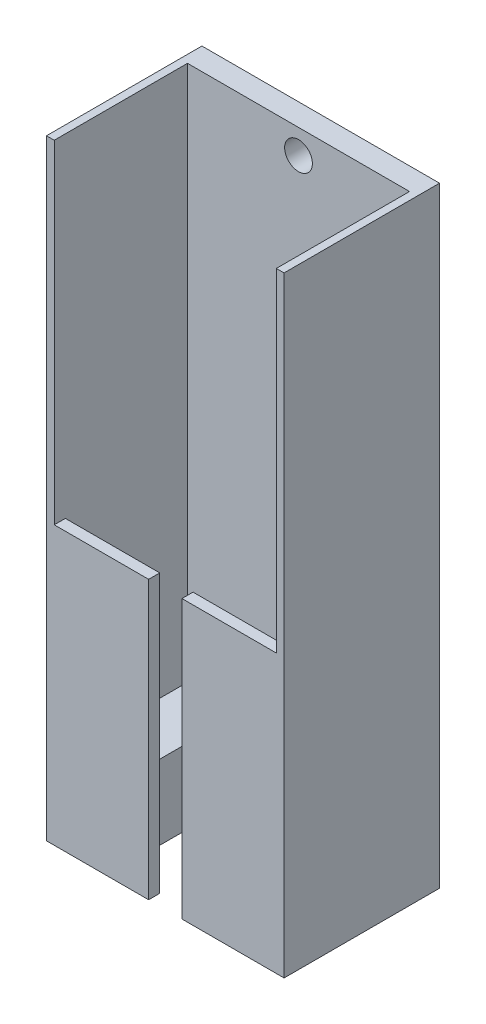
SolidWorks part; units mm, degrees
ref_plane "Front Plane" through (0, 0, 0) normal (0, 0, 1) x (1, 0, 0)
ref_plane "Top Plane" through (0, 0, 0) normal (0, 1, 0) x (1, 0, 0)
ref_plane "Right Plane" through (0, 0, 0) normal (1, 0, 0) x (0, 0, -1)
sketch "Sketch1" plane through (0, 0, 0) normal (0, 0, 1) x (1, 0, 0)
  line L1 (0, 0) -> (54.356, 0)
  line L2 (0, 0) -> (0, -139.7)
  line L3 (0, -139.7) -> (54.356, -139.7)
  line L4 (54.356, 0) -> (54.356, -139.7)
  dimension "D1" = 54.356
  dimension "D2" = 139.7
extrude "Boss-Extrude1" add sketch "Sketch1" along normal blind 35.56
ref_plane "Plane1" through (0, 0, 5.08) normal (0, 0, -1) x (-1, 0, 0)
sketch "Sketch2" plane through (0, 0, 5.08) normal (0, 0, -1) x (-1, 0, 0)
  line L1 (-1.778, -33.02) -> (-52.578, -33.02)
  line L2 (-1.778, -33.02) -> (-1.778, -122.6312)
  line L3 (-1.778, -122.6312) -> (-13.843, -122.6312)
  line L4 (-52.578, -33.02) -> (-52.578, -122.6312)
  line L5 (-1.778, -33.02) -> (-52.578, -122.6312) construction
  line L6 (-1.778, -122.6312) -> (-52.578, -33.02) construction
  line L8 (-54.356, 0) -> (0, 0) construction
  line L10 (0, -139.7) -> (-54.356, -139.7) construction
  line L11 (-13.843, -139.7) -> (-40.513, -139.7)
  line L12 (-13.843, -139.7) -> (-13.843, -122.6312)
  line L14 (-40.513, -139.7) -> (-40.513, -122.6312)
  line L15 (-13.843, -139.7) -> (-40.513, -122.6312) construction
  line L16 (-13.843, -122.6312) -> (-40.513, -139.7) construction
  line L17 (-40.513, -122.6312) -> (-52.578, -122.6312)
  point P0 (-27.178, -77.8256)
  point P8 (-41.2709, -15.2578)
  point P13 (-27.178, 0)
  point P14 (-27.178, -131.1656)
  point P19 (0, 0)
  point P20 (0, 0)
  point P21 (0, 0)
  dimension "D1" = 17.0688
  dimension "D2" = 106.68
  dimension "D3" = 50.8
  dimension "D4" = 26.67
extrude "Cut-Extrude1" cut sketch "Sketch2" against normal blind 27.94
sketch "Sketch3" plane through (0, 0, 35.56) normal (0, 0, 1) x (1, 0, 0)
  line L0 (23.368, -139.7) -> (30.988, -139.7)
  line L1 (0, -139.7) -> (54.356, -139.7) construction
  line L2 (30.988, -139.7) -> (30.988, -76.2)
  line L3 (30.988, -76.2) -> (52.578, -76.2)
  line L4 (52.578, 0) -> (1.778, 0)
  line L7 (1.778, 0) -> (1.778, -76.2)
  line L8 (1.778, -76.2) -> (23.368, -76.2)
  line L9 (23.368, -76.2) -> (23.368, -139.7)
  line L11 (52.578, -76.2) -> (52.578, 0)
  line L12 (54.356, 0) -> (0, 0) construction
  line L13 (1.778, -122.6312) -> (1.778, -33.02) construction
  line L14 (52.578, -33.02) -> (52.578, -122.6312) construction
  point P2 (0, 0)
  point P5 (27.178, -139.7)
  point P11 (2.6479, -53.34)
  point P12 (1.778, -10.16)
  point P14 (52.0842, -53.34)
  point P15 (0, 0)
  point P16 (27.178, -139.7)
  point P17 (54.0745, -53.34)
  point P19 (52.578, -10.16)
  point P20 (2.3018, 0)
  point P23 (6.5825, 0)
  dimension "D1" = 7.62
  dimension "D2" = 63.5
extrude "Cut-Extrude6" cut sketch "Sketch3" against normal blind 30.48
sketch "Sketch4" plane through (0, 0, 0) normal (0, 0, -1) x (-1, 0, 0)
  line L0 (-54.356, 0) -> (0, 0) construction
  line L1 (-52.578, 0) -> (-1.778, 0) construction
  circle A0 centre (-27.178, -5.588) radius 3.175
  point P4 (-27.178, 0)
  dimension "D1" = 6.35
  dimension "D2" = 5.588
extrude "Cut-Extrude7" cut sketch "Sketch4" against normal through all
